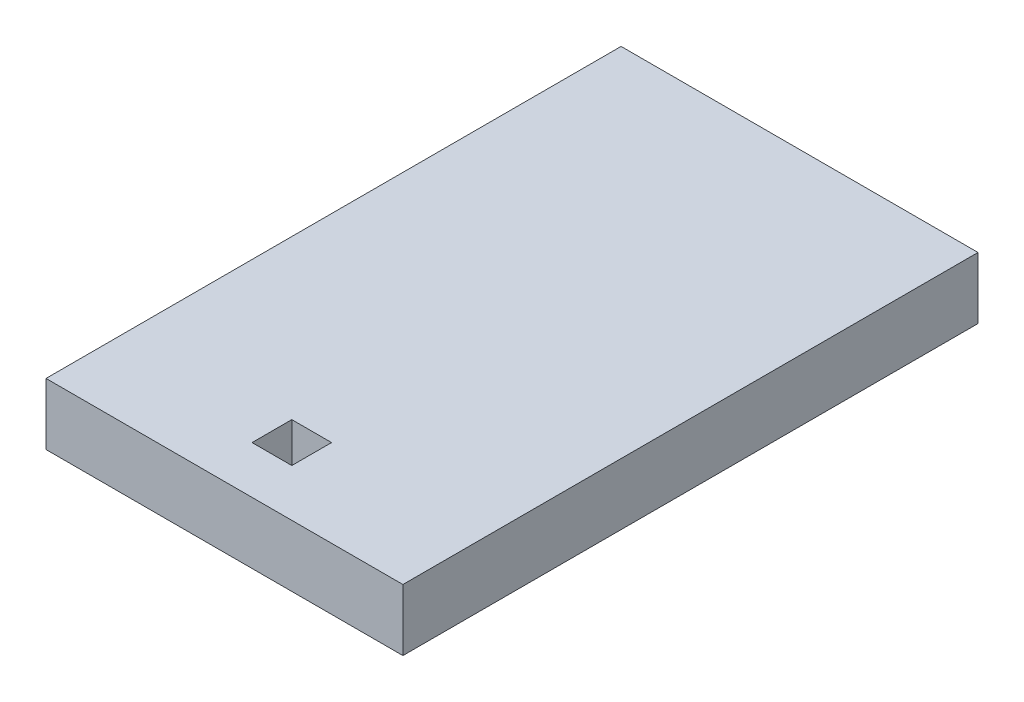
SolidWorks part; units mm, degrees
ref_plane "Front Plane" through (0, 0, 0) normal (0, 0, 1) x (1, 0, 0)
ref_plane "Top Plane" through (0, 0, 0) normal (0, 1, 0) x (1, 0, 0)
ref_plane "Right Plane" through (0, 0, 0) normal (1, 0, 0) x (0, 0, -1)
sketch "Sketch1" plane through (0, 0, 0) normal (0, 1, 0) x (1, 0, 0)
  line L0 (0, 14.8236) -> (0, 0) construction
  line L1 (-9.2, 14.8236) -> (9.2, 14.8236)
  line L2 (-9.2, 14.8236) -> (-9.2, -14.8236)
  line L3 (-9.2, -14.8236) -> (9.2, -14.8236)
  line L4 (9.2, 14.8236) -> (9.2, -14.8236)
  line L5 (0, -10.3264) -> (0, 0) construction
  line L6 (-1.025, -10.3264) -> (1.025, -10.3264)
  line L7 (-1.025, -10.3264) -> (-1.025, -12.3764)
  line L8 (-1.025, -12.3764) -> (1.025, -12.3764)
  line L9 (1.025, -10.3264) -> (1.025, -12.3764)
  line L11 (-9.2, 14.8236) -> (-12.375, 14.8236)
  line L12 (-9.2, 14.8236) -> (-9.2, -14.8236)
  line L13 (-9.2, -14.8236) -> (-12.375, -14.8236)
  line L14 (-12.375, 14.8236) -> (-12.375, -14.8236)
  point P11 (1.025, -11.3514)
  point P14 (9.2, 0)
  dimension "D1" = 18.4
  dimension "D2" = 29.6472
  dimension "D3" = 26.175
  dimension "D4" = 2.05
  dimension "D5" = 3.175
extrude "Boss-Extrude1" add sketch "Sketch1" along normal blind 3.175 contours L4 L1 L2 L3 L6 L9 L8 L7 | L11 L14 L13 L2 region at (0, 0, -0.0881) region at (-10.7875, 0, 0)
sketch "Sketch2" plane through (0, 3.175, 0) normal (0, 1, 0) x (1, 0, 0)
  line L0 (-12.375, -14.8236) -> (9.2, -14.8236) construction
  line L1 (-12.375, 14.8236) -> (-9.2, 14.8236)
  line L2 (-12.375, 14.8236) -> (-12.375, -14.8236)
  line L3 (-12.375, -14.8236) -> (-9.2, -14.8236)
  line L4 (-9.2, 14.8236) -> (-9.2, -14.8236)
  dimension "D1" = 3.175
extrude "Cut-Extrude1" cut sketch "Sketch2" against normal through all
equation "\"bottomThickness\"= .220in"
equation "\"wallThickness\"= .125in"
equation "\"D1@Sketch2\"=\"wallThickness\""
equation "\"D1@Boss-Extrude1\"=\"wallThickness\""
